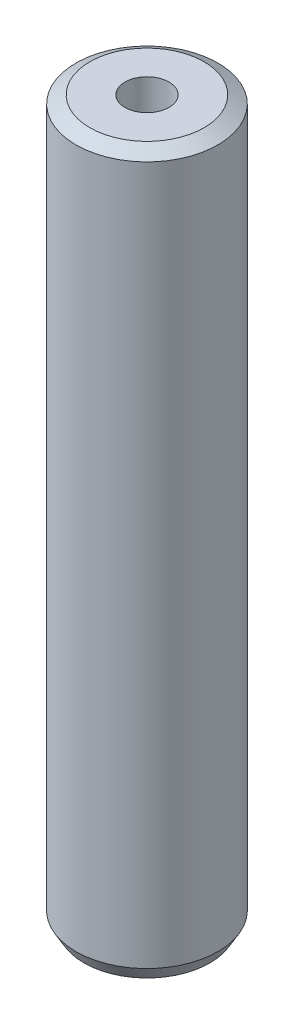
SolidWorks part; units mm, degrees
ref_plane "Front Plane" through (0, 0, 0) normal (0, 0, 1) x (1, 0, 0)
ref_plane "Top Plane" through (0, 0, 0) normal (0, 1, 0) x (1, 0, 0)
ref_plane "Right Plane" through (0, 0, 0) normal (1, 0, 0) x (0, 0, -1)
sketch "Sketch1" plane through (0, 0, 0) normal (0, 1, 0) x (1, 0, 0)
  circle A0 centre (0, 0) radius 52.5
  dimension "SHAFT_OD" = 105
extrude "Boss-Extrude1" add sketch "Sketch1" along normal blind 532.8338
sketch "Sketch2" plane through (0, 0, 0) normal (0, 1, 0) x (1, 0, 0)
  circle A0 centre (0, 0) radius 16.294
  dimension "BORE_D" = 32.588
extrude "Cut-Extrude1" cut sketch "Sketch2" along normal through all
chamfer "Chamfer1" distance 5.9098 angle 60 2 edges at (0, 532.8338, 52.5) (0, 0, 52.5) first distance on face at (0, 532.8338, 52.5) first distance on face at (0, 0, 16.294)
